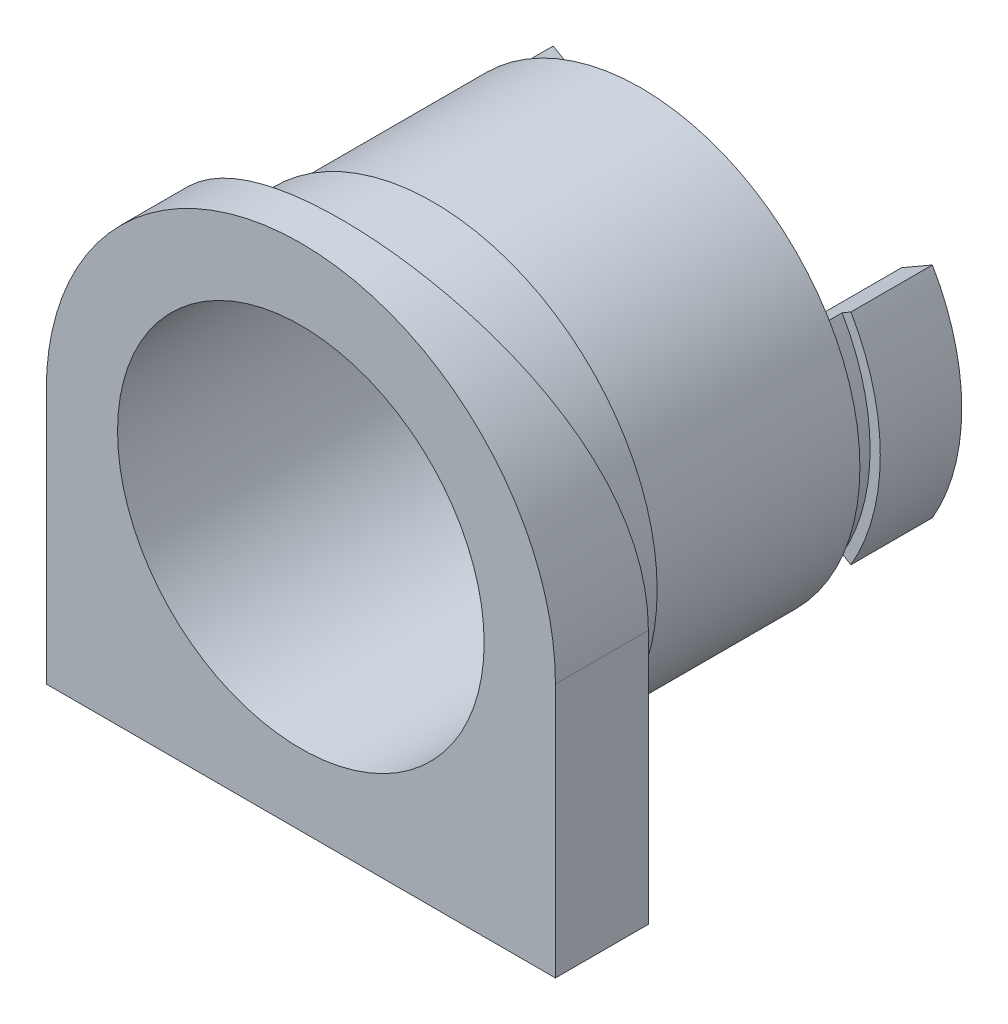
SolidWorks part; units mm, degrees
ref_plane "Спереди" through (0, 0, 0) normal (0, 0, 1) x (1, 0, 0)
ref_plane "Сверху" through (0, 0, 0) normal (0, 1, 0) x (1, 0, 0)
ref_plane "Справа" through (0, 0, 0) normal (1, 0, 0) x (0, 0, -1)
sketch "Эскиз1" plane through (0, 0, 0) normal (0, 1, 0) x (1, 0, 0)
  line L0 (0, 31.75) -> (0, -31.75) construction
  line L1 (-12.5, -29.1858) -> (12.5, -29.1858) construction
  line L2 (-12.5, -29.1858) -> (-12.5, -33.75)
  line L3 (-12.5, -33.75) -> (12.5, -33.75)
  line L4 (12.5, -33.75) -> (12.5, -29.1858)
  circle A0 centre (0, 0) radius 31.75 construction
  arc A1 (-12.5, -29.1858) -> (12.5, -29.1858) centre (0, 0) ccw
  dimension "D1" = 63.5
  dimension "D2" = 25
  dimension "D3" = 2
extrude "Вытянуть1" add sketch "Эскиз1" along normal blind 25
sketch "Эскиз2" plane through (0, 0, 33.75) normal (0, 0, 1) x (1, 0, 0)
  line L0 (12.5, 25) -> (12.5, 0) construction
  circle A0 centre (0, 12.5) radius 9
  dimension "D1" = 18
  dimension "D2" = 12.5
  dimension "D3" = 12.5
extrude "Вытянуть2" cut sketch "Эскиз2" against normal through all
sketch "Эскиз3" plane through (0, 0, 33.75) normal (0, 0, 1) x (1, 0, 0)
  circle A0 centre (0, 12.5) radius 9
  circle A1 centre (0, 12.5) radius 9 construction
  circle A2 centre (0, 12.5) radius 11
  dimension "D1" = 22
extrude "tube" add sketch "Эскиз3" against normal blind 16.7
sketch "Эскиз4" plane through (0, 0, 17.05) normal (0, 0, -1) x (-1, 0, 0)
  line L0 (7.7942, 17) -> (9.5263, 18)
  line L1 (7.7942, 8) -> (9.5263, 7)
  line L2 (0, 12.5) -> (11, 12.5) construction
  line L3 (0, 12.5) -> (9.5263, 18) construction
  line L4 (0, 12.5) -> (9.5263, 7) construction
  line L5 (-7.7942, 8) -> (-9.5263, 7)
  line L6 (-7.7942, 17) -> (-9.5263, 18)
  line L7 (0, 12.5) -> (-9.5263, 7) construction
  line L8 (0, 12.5) -> (-9.5263, 18) construction
  circle A0 centre (0, 12.5) radius 9 construction
  circle A1 centre (0, 12.5) radius 11 construction
  circle A2 centre (0, 12.5) radius 11 construction
  arc A3 (7.7942, 17) -> (7.7942, 8) centre (0, 12.5) cw
  arc A4 (9.5263, 18) -> (9.5263, 7) centre (0, 12.5) cw
  arc A5 (-7.7942, 8) -> (-7.7942, 17) centre (0, 12.5) cw
  arc A6 (-9.5263, 7) -> (-9.5263, 18) centre (0, 12.5) cw
  dimension "D1" = 30
  dimension "D2" = 30
extrude "support" add sketch "Эскиз4" along normal blind 5
sketch "Эскиз5" plane through (0, 0, 12.05) normal (0, 0, -1) x (-1, 0, 0)
  circle A0 centre (0, 12.5) radius 11
  circle A1 centre (0, 12.5) radius 10.75
  circle A2 centre (0, 12.5) radius 11 construction
  dimension "D1" = 21.5
extrude "holder" cut sketch "Эскиз5" against normal blind 15.205
ref_axis "Ось2" through (0, 12.5, 12.05) along (0, 0, 1)
sketch "Эскиз7" plane through (-5.4127, 9.375, 0) normal (-0.5, 0.866, 0) x (0.866, 0.5, 0)
  line L1 (17, -17.05) -> (16.5, -17.05)
  line L2 (17, -17.05) -> (17, -16.05)
  line L3 (17, -16.05) -> (16.5, -16.05)
  line L4 (16.5, -17.05) -> (16.5, -16.05)
  dimension "D1" = 1
  dimension "D2" = 0.5
revolve "Вырез-Повернуть2" cut sketch "Эскиз7" angle 360 about axis through (0, 12.5, 12.05) along (0, 0, 1)
sketch "Эскиз8" plane through (0, 0, 33.75) normal (0, 0, 1) x (1, 0, 0)
  line L0 (-12.5, 25) -> (-12.5, 0) construction
  line L1 (12.5, 25) -> (12.5, 0) construction
  line L2 (-12.5, 25) -> (12.5, 25) construction
  line L3 (-12.5, 12.5) -> (-12.5, 0)
  line L4 (-12.5, 0) -> (12.5, 0)
  line L5 (12.5, 0) -> (12.5, 12.5)
  arc A0 (-12.5, 12.5) -> (12.5, 12.5) centre (0, 12.5) cw
  circle A1 centre (0, 12.5) radius 9 construction
extrude "Вытянуть3" cut sketch "Эскиз8" against normal blind 10 flip side to cut
